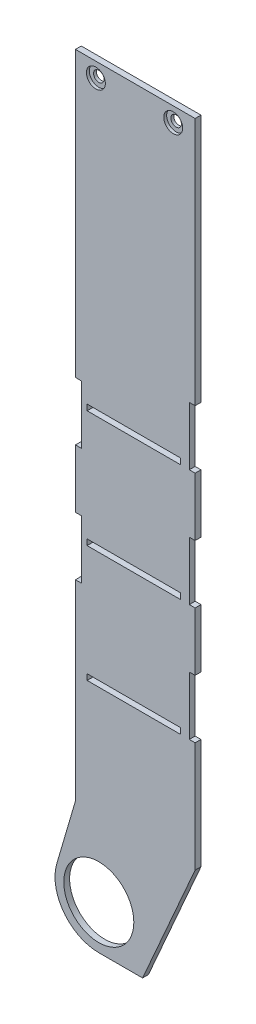
SolidWorks part; units mm, degrees
ref_plane "前视基准面" through (0, 0, 0) normal (0, 0, 1) x (1, 0, 0)
ref_plane "上视基准面" through (0, 0, 0) normal (0, 1, 0) x (1, 0, 0)
ref_plane "右视基准面" through (0, 0, 0) normal (1, 0, 0) x (0, 0, -1)
sketch "草图1" plane through (0, 0, 0) normal (0, 0, 1) x (1, 0, 0)
  line L93 (-8, -48.3425) -> (-6, -48.3425)
  line L100 (-6, -48.3425) -> (-6, -68.3425)
  line L101 (-6, -68.3425) -> (-8, -68.3425)
  line L102 (-8, -68.3425) -> (-8, -88.3425)
  line L103 (-8, -88.3425) -> (-6, -88.3425)
  line L104 (-6, -88.3425) -> (-6, -108.3425)
  line L105 (-6, -108.3425) -> (-8, -108.3425)
  line L106 (-8, -108.3425) -> (-8, -128.3425)
  line L108 (33, -36.2215) -> (31, -36.2215)
  line L109 (31, -36.2215) -> (31, -56.2215)
  line L110 (31, -56.2215) -> (33, -56.2215)
  line L111 (33, -56.2215) -> (33, -76.2215)
  line L112 (33, -76.2215) -> (31, -76.2215)
  line L113 (31, -76.2215) -> (31, -96.2215)
  line L114 (31, -96.2215) -> (33, -96.2215)
  line L117 (33, -96.2215) -> (33, -116.2215)
  line L118 (33, -116.2215) -> (31, -116.2215)
  line L119 (31, -116.2215) -> (31, -136.2215)
  line L120 (31, -136.2215) -> (33, -136.2215)
  line L121 (33, -136.2215) -> (33, -174)
  line L124 (-8, 49) -> (33, 49)
  line L128 (-4, -56.2215) -> (-4, -54.2215)
  line L129 (-4, -54.2215) -> (28, -54.2215)
  line L130 (28, -54.2215) -> (28, -56.2215)
  line L131 (-4, -56.2215) -> (28, -56.2215)
  line L134 (-4, -94.2215) -> (28, -94.2215)
  line L135 (-4, -96.2215) -> (28, -96.2215)
  line L136 (28, -94.2215) -> (28, -96.2215)
  line L137 (-4, -96.2215) -> (-4, -94.2215)
  line L138 (-4, -134.2215) -> (28, -134.2215)
  line L139 (-4, -136.2215) -> (28, -136.2215)
  line L140 (28, -134.2215) -> (28, -136.2215)
  line L141 (-4, -136.2215) -> (-4, -134.2215)
  line L145 (-8, -174) -> (-8, -128.3425)
  line L146 (-8, -174) -> (-14.3926, -195.7746)
  line L148 (0, -215) -> (15, -215)
  line L151 (15, -215) -> (33, -174)
  line L153 (-8, 49) -> (-8, -48.3425)
  line L154 (33, 49) -> (33, -36.2215)
  arc A61 (-14.3926, -195.7746) -> (0, -215) centre (0, -200) ccw
  circle A62 centre (0, -200) radius 12
  dimension "D1" = 3
extrude "凸台-拉伸1" add sketch "草图1" along normal blind 2 contours L154 L108 L109 L110 L111 L112 L113 L114 L117 L118 L119 L120 L121 L151 L148 A61 L146 L145 L106 L105 L104 L103 L102 L101 L100 L93 L153 L124 | L128 L129 L130 L131 | L134 L136 L135 L137 | L138 L140 L139 L141 | A62
hole_wizard "M3 六角凹头盖的柱孔1" positions "3D草图1" profile "草图2" counterbore size "M3" standard "BSI" end condition through all
sketch3d "3D草图1"
  line L10 (-1, 44, 2) -> (25.5, 44, 2)
  point P33 (-1, 44, 2)
  point P40 (25.5, 44, 2)
sketch "草图2" plane through (-1, 44, 2) normal (1, 0, 0) x (0, -1, 0)
  line L0 (0, 0) -> (0, 2)
  line L1 (0, 2) -> (1.8, 2)
  line L3 (1.8, 2) -> (1.8, 1)
  line L4 (1.8, 1) -> (3.25, 1)
  line L5 (3.25, 1) -> (3.25, 0)
  line L7 (3.25, 0) -> (0, 0)
  line L11 (0, -6.35) -> (0, 107.95) construction
  dimension "通孔孔直径" = 3.6
  dimension "通孔孔深度" = 2
  dimension "柱形沉头孔直径" = 6.5
  dimension "柱形沉头孔深度" = 1
